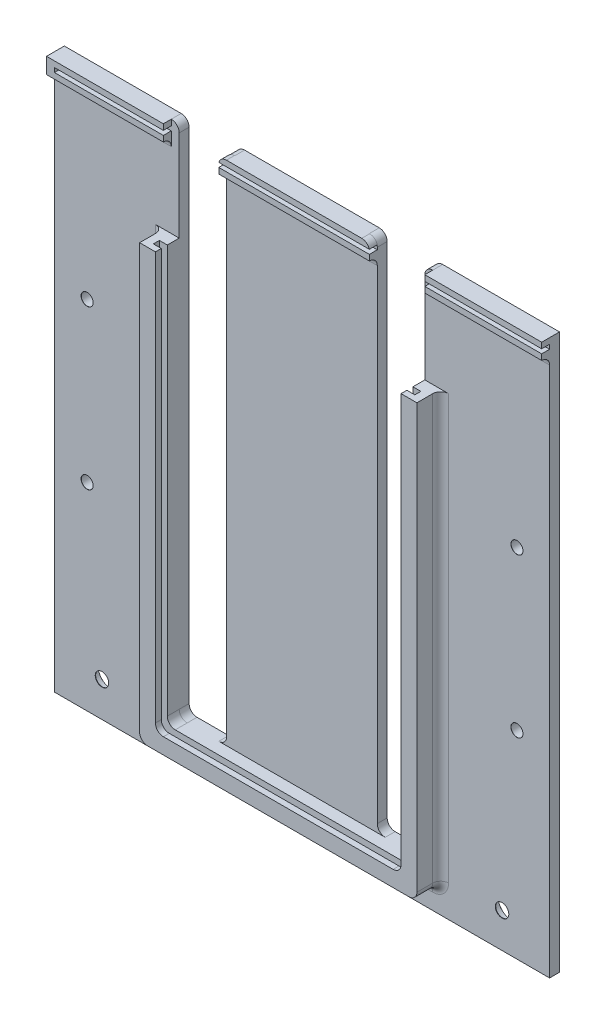
SolidWorks part; units mm, degrees
ref_plane "Plano frontal" through (0, 0, 0) normal (0, 0, 1) x (1, 0, 0)
ref_plane "Plano superior" through (0, 0, 0) normal (0, 1, 0) x (1, 0, 0)
ref_plane "Plano direito" through (0, 0, 0) normal (1, 0, 0) x (0, 0, -1)
sketch "Esboço1" plane through (0, 0, 0) normal (0, 0, 1) x (1, 0, 0)
  line L0 (10.1406, 22.9022) -> (10.1406, -117.0978) construction
  line L1 (-52.3594, 22.9022) -> (72.6406, 22.9022)
  line L2 (-52.3594, 22.9022) -> (-52.3594, -117.0978)
  line L3 (-52.3594, -117.0978) -> (72.6406, -117.0978)
  line L4 (72.6406, 22.9022) -> (72.6406, -117.0978)
  line L5 (-52.3594, -47.0978) -> (72.6406, -47.0978) construction
  dimension "D1" = 125
  dimension "D2" = 140
extrude "Ressalto-extrusão1" add sketch "Esboço1" along normal blind 2.5
sketch "Esboço2" plane through (0, 0, 2.5) normal (0, 0, 1) x (1, 0, 0)
  line L0 (-52.3594, -47.0978) -> (72.6406, -47.0978) construction
  line L1 (-52.3594, 22.9022) -> (-52.3594, -117.0978) construction
  line L2 (72.6406, -117.0978) -> (72.6406, 22.9022) construction
  line L3 (10.1406, 22.9022) -> (10.1406, -117.0978) construction
  line L4 (72.6406, 22.9022) -> (-52.3594, 22.9022) construction
  line L5 (-52.3594, -117.0978) -> (72.6406, -117.0978) construction
  line L7 (-24.8594, -2.0978) -> (-20.8594, -2.0978)
  line L8 (-24.8594, -2.0978) -> (-24.8594, -107.0978)
  line L9 (-24.8594, -107.0978) -> (-23.8742, -107.0978)
  line L10 (-20.8594, -2.0978) -> (-20.8594, -107.0978)
  line L11 (41.1406, -2.0978) -> (41.1406, -107.0978)
  line L12 (45.1406, -2.0978) -> (41.1406, -2.0978)
  line L13 (45.1406, -2.0978) -> (45.1406, -107.0978)
  line L14 (-20.8594, -107.0978) -> (41.1406, -107.0978)
  line L15 (-24.8594, -107.0978) -> (-23.8742, -107.0978)
  line L16 (-24.8594, -107.0978) -> (-24.8594, -111.0978)
  line L17 (-24.8594, -111.0978) -> (45.1406, -111.0978)
  line L18 (45.1406, -107.0978) -> (45.1406, -111.0978)
  dimension "D1" = 35
  dimension "D2" = 105
  dimension "D3" = 4
  dimension "D4" = 115
  dimension "D5" = 4
extrude "Ressalto-extrusão2" add sketch "Esboço2" along normal blind 6 contours L16 L17 L18 L13 L12 L11 L14 L10 L7 L8
sketch "Esboço3" plane through (41.1406, 0, 0) normal (-1, 0, 0) x (0, 0, 1)
  line L0 (8.5, -2.0978) -> (2.5, -2.0978) construction
  line L1 (5.5, -2.0978) -> (7.02, -2.0978)
  line L2 (5.5, -2.0978) -> (5.5, -107.0978)
  line L3 (5.5, -107.0978) -> (7.02, -107.0978)
  line L4 (7.02, -2.0978) -> (7.02, -107.0978)
  line L5 (8.5, -107.0978) -> (2.5, -107.0978) construction
  line L6 (5.5, -2.0978) -> (0.5363, -2.0978) construction
  line L7 (7.02, -2.0978) -> (8.5, -2.0978) construction
  line L8 (2.5, -2.0978) -> (2.5, -107.0978) construction
  line L9 (8.5, -2.0978) -> (8.5, -107.0978) construction
  dimension "D1" = 1.52
  dimension "D2" = 3
  dimension "D3" = 1.48
extrude "Corte-extrusão1" cut sketch "Esboço3" against normal blind 2
sketch "Esboço4" plane through (-20.8594, 0, 0) normal (1, 0, 0) x (0, 0, -1)
  line L0 (-8.5, -2.0978) -> (-2.5, -2.0978) construction
  line L1 (-7.02, -2.0978) -> (-5.5, -2.0978)
  line L2 (-7.02, -2.0978) -> (-7.02, -107.0978)
  line L3 (-7.02, -107.0978) -> (-5.5, -107.0978)
  line L4 (-5.5, -2.0978) -> (-5.5, -107.0978)
  line L5 (-8.5, -107.0978) -> (-2.5, -107.0978) construction
  line L6 (-8.5, -2.0978) -> (-7.02, -2.0978) construction
  line L7 (-5.5, -2.0978) -> (-2.5, -2.0978) construction
  line L9 (-2.5, -2.0978) -> (-2.5, -107.0978) construction
  line L10 (-8.5, -2.0978) -> (-8.5, -107.0978) construction
  dimension "D1" = 1.52
  dimension "D2" = 3
  dimension "D3" = 1.48
extrude "Corte-extrusão2" cut sketch "Esboço4" against normal blind 2
sketch "Esboço5" plane through (0, -107.0978, 0) normal (0, 1, 0) x (1, 0, 0)
  line L5 (-22.8594, -5.5) -> (43.1406, -5.5)
  line L6 (-22.8594, -5.5) -> (-22.8594, -7.02)
  line L7 (-22.8594, -7.02) -> (43.1406, -7.02)
  line L8 (43.1406, -5.5) -> (43.1406, -7.02)
extrude "Corte-extrusão3" cut sketch "Esboço5" against normal blind 2
fillet "Filete1" radius 2 4 edges at (41.1406, -107.0978, 4) (41.1406, -107.0978, 7.76) (-20.8594, -107.0978, 4) (-20.8594, -107.0978, 7.76)
fillet "Filete2" radius 2 2 edges at (-24.8594, -111.0978, 5.5) (45.1406, -111.0978, 5.5)
fillet "Filete3" radius 2 5 edges at (45.1406, -55.5978, 2.5) (44.5548, -110.512, 2.5) (10.1406, -111.0978, 2.5) (-24.2736, -110.512, 2.5) (-24.8594, -55.5978, 2.5)
sketch "Esboço6" plane through (0, 0, 2.5) normal (0, 0, 1) x (1, 0, 0)
  line L0 (-20.8594, -2.0978) -> (41.1406, -2.0978) construction
  line L1 (10.1406, -2.0978) -> (10.1406, -41.1152) construction
  line L2 (-14.8594, -2.0978) -> (-14.8594, -50.9519) construction
  line L3 (-20.8594, -2.0978) -> (-20.8594, -105.0978) construction
  line L4 (72.6406, 22.9022) -> (-52.3594, 22.9022) construction
  line L5 (-20.8594, 22.9022) -> (-8.8594, 22.9022)
  line L6 (-20.8594, 22.9022) -> (-20.8594, -107.0978)
  line L7 (-20.8594, -107.0978) -> (-8.8594, -107.0978)
  line L8 (-8.8594, 22.9022) -> (-8.8594, -107.0978)
  line L9 (-18.8594, -107.0978) -> (39.1406, -107.0978) construction
  line L10 (41.1406, -107.0978) -> (29.1406, -107.0978)
  line L11 (29.1406, 22.9022) -> (29.1406, -107.0978)
  line L12 (41.1406, 22.9022) -> (29.1406, 22.9022)
  line L13 (41.1406, 22.9022) -> (41.1406, -107.0978)
  dimension "D1" = 6
  dimension "D2" = 12
extrude "Corte-extrusão4" cut sketch "Esboço6" against normal through all
fillet "Filete4" radius 2 4 edges at (-20.8594, 22.9022, 1.25) (-8.8594, 22.9022, 1.25) (41.1406, 22.9022, 1.25) (29.1406, 22.9022, 1.25)
fillet "Filete5" radius 2 6 edges at (-20.8594, -106.0978, 2.5) (-20.8594, -107.0978, 1.25) (-8.8594, -107.0978, 1.25) (41.1406, -106.0978, 2.5) (41.1406, -107.0978, 1.25) (29.1406, -107.0978, 1.25)
sketch "Esboço7" plane through (0, 0, 2.5) normal (0, 0, 1) x (1, 0, 0)
  line L0 (72.6406, -117.0978) -> (72.6406, 22.9022) construction
  line L1 (-52.3594, 22.9022) -> (72.6406, 22.9022)
  line L2 (-52.3594, 22.9022) -> (-52.3594, 18.9022)
  line L3 (-52.3594, 18.9022) -> (72.6406, 18.9022)
  line L4 (72.6406, 22.9022) -> (72.6406, 18.9022)
  line L5 (-22.8594, 22.9022) -> (-22.8594, 18.9022)
  line L6 (10.1406, 22.9022) -> (10.1406, 18.9022) construction
  line L7 (43.1406, 22.9022) -> (43.1406, 18.9022)
  line L8 (-8.8692, 18.9022) -> (-8.8692, 22.9022)
  line L9 (29.1406, 18.9022) -> (29.1406, 22.9022)
  line L10 (29.1406, 20.9022) -> (29.1406, -105.0978) construction
  line M9 (-22.8594, 22.9022) -> (-52.3594, 22.9022)
  line M10 (-52.3594, 22.9022) -> (-52.3594, -117.0978)
  line M12 (72.6406, -117.0978) -> (72.6406, 22.9022)
  line M13 (72.6406, 22.9022) -> (43.1406, 22.9022)
  dimension "D1" = 4
extrude "Ressalto-extrusão3" add sketch "Esboço7" along normal blind 2 contours L6 L1 L8 L3 | L1 L6 L3 L9 | L5 L3 M9 M10 | L7 L3 M13 M12
sketch "Esboço8" plane through (0, 0, 4.5) normal (0, 0, 1) x (1, 0, 0)
  line L0 (72.6406, 18.9022) -> (72.6406, 22.9022) construction
  line L1 (-50.3594, 21.4522) -> (72.6406, 21.4522)
  line L2 (-50.3594, 21.4522) -> (-50.3594, 20.3522)
  line L3 (-50.3594, 20.3522) -> (72.6406, 20.3522)
  line L4 (72.6406, 21.4522) -> (72.6406, 20.3522)
  line L5 (72.6406, 22.9022) -> (72.6406, 21.4522) construction
  line L6 (72.6406, 20.3522) -> (72.6406, 18.9022) construction
  line L7 (-52.3594, 22.9022) -> (-52.3594, 18.9022) construction
  dimension "D1" = 1.1
  dimension "D2" = 2
extrude "Corte-extrusão5" cut sketch "Esboço8" against normal blind 2
fillet "Filete6" radius 2 3 edges at (10.1406, 18.9022, 2.5) (29.1406, 22.9022, 3.5) (-8.8692, 22.9022, 3.5)
sketch "Esboço9" plane through (0, 0, 2.5) normal (0, 0, 1) x (1, 0, 0)
  line L0 (10.1357, 22.9022) -> (10.1406, -117.0978) construction
  line L1 (-6.9463, 22.9022) -> (27.2177, 22.9022) construction
  line L2 (-52.3594, -117.0978) -> (72.6406, -117.0978) construction
  line L3 (-52.3594, -50.0978) -> (72.6406, -50.0978) construction
  line L4 (-52.3594, 16.9022) -> (-52.3594, -117.0978) construction
  line L5 (72.6406, -117.0978) -> (72.6406, 16.9022) construction
  line L6 (-44.1094, -50.0978) -> (-44.1094, -1.2846) construction
  line L7 (-44.1094, -27.0978) -> (-52.3594, -27.0978) construction
  line L8 (-52.3594, -24.0978) -> (-52.3594, -30.0978)
  line L9 (-52.3594, -24.0978) -> (-39.8594, -24.0978)
  line L10 (-52.3594, -24.0978) -> (-52.3594, -30.0978)
  line L11 (-52.3594, -30.0978) -> (-39.8594, -30.0978)
  line L12 (-39.8594, -24.0978) -> (-39.8594, -30.0978)
  line L14 (-39.8594, -70.0978) -> (-39.8594, -64.0978)
  line L18 (-52.3594, -64.0978) -> (-39.8594, -64.0978)
  line L19 (-52.3594, -64.0978) -> (-52.3594, -70.0978)
  line L20 (-52.3594, -70.0978) -> (-39.8594, -70.0978)
  line L21 (72.6369, -64.0935) -> (72.6373, -70.0935)
  line L22 (72.6369, -64.0935) -> (60.1369, -64.0943)
  line L23 (60.1373, -70.0943) -> (60.1369, -64.0943)
  line L24 (72.6373, -70.0935) -> (60.1373, -70.0943)
  line L25 (72.6345, -30.0935) -> (60.1345, -30.0943)
  line L26 (60.1341, -24.0943) -> (60.1345, -30.0943)
  line L27 (72.6341, -24.0935) -> (60.1341, -24.0943)
  line L28 (72.6341, -24.0935) -> (72.6345, -30.0935)
  line L29 (-44.1094, -50.0978) -> (-44.1094, -70.0978) construction
  line L30 (-52.3594, -67.0978) -> (-39.8594, -67.0978) construction
  line L31 (64.3906, 16.9022) -> (64.3906, -70.094) construction
  line L32 (72.6406, 16.9022) -> (43.1406, 16.9022) construction
  line L33 (60.1343, -27.0943) -> (72.6343, -27.0935) construction
  line L34 (60.1371, -67.0943) -> (72.6371, -67.0935) construction
  point P21 (-39.8594, -27.0978)
  point P25 (-39.8594, -67.0978)
  point P37 (-44.1094, -67.0978)
  point P46 (64.3906, -27.094)
  point P47 (64.3906, -67.094)
  dimension "D3" = 17
  dimension "D1" = 8.25
  dimension "D2" = 23
  dimension "D4" = 6
  dimension "D5" = 12.5
  dimension "D6" = 6
  dimension "D7" = 12.5
  dimension "D8" = 8.25
hole_wizard "Furos-guia com Ø3.0mm1" positions "Esboço10" profile "Esboço11" hole size "Ø3.0" standard "ISO" end condition through all
sketch "Esboço10" plane through (0, 0, 2.5) normal (0, 0, 1) x (1, 0, 0)
  point P0 (-44.1094, -27.0978)
  point P3 (-44.1094, -67.0978)
  point P6 (64.3906, -27.094)
  point P9 (64.3906, -67.094)
sketch "Esboço11" plane through (-44.1094, -27.0978, 2.5) normal (1, 0, 0) x (0, -1, 0)
  line L0 (0, 0) -> (0, 2.5)
  line L1 (0, 2.5) -> (1.5, 2.5)
  line L2 (1.5, 2.5) -> (1.5, 0.025)
  line L3 (1.5, 0.025) -> (1.525, 0)
  line L5 (1.525, 0) -> (0, 0)
  line L6 (-1.5, 0.025) -> (-1.525, 0) construction
  line L11 (0, -6.35) -> (0, 107.95) construction
  dimension "Thru Hole Dia." = 3
  dimension "Thru Hole Depth" = 2.5
  dimension "Near C'Sink Dia." = 3.05
  dimension "Near C'Sink Angle" = 90
sketch "Esboço12" plane through (0, 0, 0) normal (0, 0, -1) x (-1, 0, 0)
  line L0 (-10.1406, -117.0978) -> (-10.1406, -88.6993) construction
  line L1 (52.3594, -117.0978) -> (-72.6406, -117.0978) construction
  line L2 (-72.6406, -108.2978) -> (-60.6406, -108.2978) construction
  line L3 (-72.6406, -117.0978) -> (-72.6406, 22.9022) construction
  line L4 (-60.6406, -108.2978) -> (-60.6406, -117.0978) construction
  circle A0 centre (-60.6406, -108.2978) radius 2.8052
  circle A1 centre (40.3594, -108.2978) radius 2.8052
  dimension "D1" = 12
  dimension "D2" = 8.8
hole_wizard "Rebaixo para parafuso com cabeça panela de M31" positions "Esboço13" profile "Esboço14" counterbore size "M3" standard "ISO" end condition through all
sketch "Esboço13" plane through (0, 0, 0) normal (0, 0, -1) x (-1, 0, 0)
  point P0 (40.3594, -108.2978)
  point P3 (-60.6406, -108.2978)
sketch "Esboço14" plane through (-40.3594, -108.2978, 0) normal (1, 0, 0) x (0, 1, 0)
  line L0 (0, 0) -> (0, 8.5)
  line L1 (0, 8.5) -> (1.7, 8.5)
  line L3 (1.7, 8.5) -> (1.7, 2.4)
  line L4 (3.5, 2.4) -> (1.7, 2.4)
  line L5 (3.5, 2.4) -> (3.5, 0.025)
  line L6 (3.5, 0.025) -> (3.525, 0)
  line L7 (3.525, 0) -> (0, 0)
  line L8 (-3.5, 0.025) -> (-3.525, 0) construction
  line L11 (0, -6.35) -> (0, 107.95) construction
  dimension "Thru Hole Dia." = 3.4
  dimension "Thru Hole Depth" = 8.5
  dimension "C'Bore Dia." = 7
  dimension "C'Bore Depth" = 2.4
  dimension "Near C'Sink Dia." = 7.05
  dimension "Near C'Sink Angle" = 90
